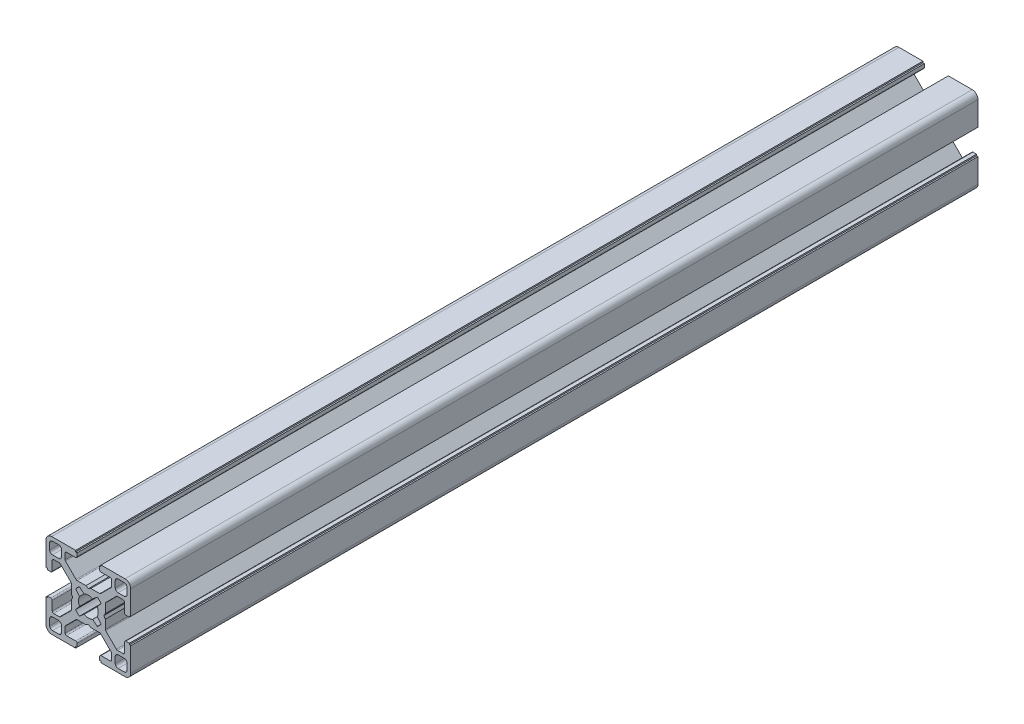
SolidWorks part; units mm, degrees
ref_plane "Front Plane" through (0, 0, 0) normal (0, 0, 1) x (1, 0, 0)
ref_plane "Top Plane" through (0, 0, 0) normal (0, 1, 0) x (1, 0, 0)
ref_plane "Right Plane" through (0, 0, 0) normal (1, 0, 0) x (0, 0, -1)
sketch "Sketch1" plane through (0, 0, 0) normal (0, 0, 1) x (1, 0, 0)
  line L0 (-15, 0) -> (15, 0) construction
  line L1 (0, -15) -> (0, 15) construction
  line L2 (-4.5, 15) -> (4.5, 15) construction
  line L3 (-4, -15) -> (4, -15) construction
  line L4 (-4.5, 15) -> (-4.5, 14.5)
  line L5 (-4.5, 14.5) -> (-4, 14.5)
  line L6 (-4, 14.5) -> (-4, 13.29)
  line L7 (-4.5, 12.79) -> (-7.7675, 12.79)
  line L8 (-8.2675, 12.29) -> (-8.2675, 10.2707)
  line L9 (-8.1211, 9.9171) -> (-4.3504, 6.1464)
  line L10 (-3.9968, 6) -> (0, 6)
  line L11 (0, 0) -> (-15, 15) construction
  line L12 (-4.5, 15) -> (-12.968, 15)
  line L14 (-12.705, 9.5135) -> (-10.5135, 9.5135)
  line L15 (-13.705, 10.5135) -> (-13.705, 12.705)
  line L16 (-12.705, 13.705) -> (-10.5135, 13.705)
  line L17 (-9.5135, 10.5135) -> (-9.5135, 12.705)
  line L18 (-13.705, 9.5135) -> (-9.5135, 13.705) construction
  line L19 (-13.705, 13.705) -> (-9.5135, 9.5135) construction
  line L20 (-3.1568, 4.5038) -> (-1.5303, 3.1477) construction
  line L21 (-4.5038, 3.1568) -> (-3.1477, 1.5303) construction
  line L22 (-6, 3.9968) -> (-6, 0)
  line L23 (-9.9171, 8.1211) -> (-6.1464, 4.3504)
  line L24 (-15, 4.5) -> (-15, 12.968)
  line L25 (-12.29, 8.2675) -> (-10.2707, 8.2675)
  line L26 (-12.79, 4.5) -> (-12.79, 7.7675)
  line L27 (-14.5, 4) -> (-13.29, 4)
  line L28 (-14.5, 4.5) -> (-14.5, 4)
  line L29 (-15, 4.5) -> (-14.5, 4.5)
  circle A0 centre (0, 0) radius 3.5
  arc A1 (-12.968, 15) -> (-15, 12.968) centre (-12.968, 12.968) ccw
  circle A2 centre (0, 0) radius 5.5 construction
  arc A3 (-10.5135, 9.5135) -> (-9.5135, 10.5135) centre (-10.5135, 10.5135) ccw
  arc A4 (-13.705, 12.705) -> (-12.705, 13.705) centre (-12.705, 12.705) cw
  arc A5 (-10.5135, 13.705) -> (-9.5135, 12.705) centre (-10.5135, 12.705) cw
  arc A6 (-12.705, 9.5135) -> (-13.705, 10.5135) centre (-12.705, 10.5135) cw
  arc A7 (-12.79, 4.5) -> (-13.29, 4) centre (-13.29, 4.5) cw
  arc A8 (-12.29, 8.2675) -> (-12.79, 7.7675) centre (-12.29, 7.7675) ccw
  arc A9 (-9.9171, 8.1211) -> (-10.2707, 8.2675) centre (-10.2707, 7.7675) ccw
  arc A10 (-6, 3.9968) -> (-6.1464, 4.3504) centre (-6.5, 3.9968) ccw
  arc A11 (-4.3504, 6.1464) -> (-3.9968, 6) centre (-3.9968, 6.5) ccw
  arc A12 (-4, 13.29) -> (-4.5, 12.79) centre (-4.5, 13.29) cw
  arc A13 (-7.7675, 12.79) -> (-8.2675, 12.29) centre (-7.7675, 12.29) ccw
  arc A14 (-8.2675, 10.2707) -> (-8.1211, 9.9171) centre (-7.7675, 10.2707) ccw
  point P4 (0, 0)
  point P8 (0, 0)
  point P13 (0, 15)
  point P15 (0, -15)
  point P16 (0, 6)
  point P23 (-11.6092, 11.6093)
  point P26 (0, 6)
  point P62 (-12.79, 4)
  point P65 (-12.79, 8.2675)
  point P68 (-10.0636, 8.2675)
  point P71 (-6, 4.2039)
  point P74 (-4.2039, 6)
  point P77 (-4, 12.79)
  point P80 (-8.2675, 12.79)
  point P83 (-8.2675, 10.0636)
  dimension "Center Hole Diameter" = 7
  dimension "D11" = 2.032
  dimension "D9" = 11
  dimension "D13" = 1
  dimension "D14" = 0.5
  dimension "Rail Height" = 30
  dimension "Rail Width" = 30
  dimension "T-Slot Width" = 8
  dimension "T-Slot Depth" = 9
  dimension "D1" = 9
  dimension "D2" = 45
  dimension "D3" = 8
  dimension "D4" = 2.21
  dimension "D5" = 16.535
  dimension "D7" = 2.54
  dimension "D6" = 1.295
  dimension "D8" = 1.246
  dimension "D10" = 10.36
  dimension "D12" = 1.905
sketch "Sketch2" plane through (0, 0, 0) normal (1, 0, 0) x (0, 0, -1)
  line L0 (-76.2, 0) -> (76.2, 0) construction
  line L2 (0, -15) -> (0, 15) construction
  line L3 (0, -15) -> (0, 15) construction
  line L4 (-76.2, -15) -> (-76.2, 15) construction
  line L5 (76.2, -15) -> (76.2, 15) construction
  point P0 (-38.7, 0)
  point P3 (0, 0)
  point P4 (38.7, 0)
  point P12 (-76.2, 0)
  point P14 (76.2, 0)
  dimension "Length" = 152.4
  dimension "D1" = 37.5
sketch "Sketch3" plane through (0, 0, 0) normal (0, 0, 1) x (1, 0, 0)
  line L0 (-4.5038, 3.1568) -> (-3.1477, 1.5303)
  line L1 (0, 3.5) -> (0, 5.5)
  line L2 (-5.5, 0) -> (-3.5, 0)
  line L7 (-6, 3.9968) -> (-6, 0) construction
  line L31 (-9.9171, 8.1211) -> (-6.1464, 4.3504) construction
  line L117 (-12.29, 8.2675) -> (-10.2707, 8.2675) construction
  line L118 (-12.79, 4.5) -> (-12.79, 7.7675) construction
  line L157 (-12.705, 9.5135) -> (-10.5135, 9.5135)
  line L158 (-9.5135, 10.5135) -> (-9.5135, 12.705)
  line L163 (-10.5135, 13.705) -> (-12.705, 13.705)
  line L164 (-13.705, 12.705) -> (-13.705, 10.5135)
  line L165 (-12.705, 9.5135) -> (-10.5135, 9.5135)
  line L166 (-9.5135, 10.5135) -> (-9.5135, 12.705)
  line L167 (-10.5135, 13.705) -> (-12.705, 13.705)
  line L168 (-13.705, 12.705) -> (-13.705, 10.5135)
  line L169 (-14.5, 4) -> (-13.29, 4) construction
  line L170 (-14.5, 4.5) -> (-14.5, 4) construction
  line L171 (-15, 4.5) -> (-14.5, 4.5) construction
  line L172 (-15, 4.5) -> (-15, 12.968) construction
  line L173 (-4.5, 15) -> (-12.968, 15) construction
  line L174 (-4.5, 15) -> (-4.5, 14.5) construction
  line L175 (-4.5, 14.5) -> (-4, 14.5) construction
  line L176 (-4, 14.5) -> (-4, 13.29) construction
  line L177 (-4.5, 12.79) -> (-7.7675, 12.79) construction
  line L178 (-8.2675, 12.29) -> (-8.2675, 10.2707) construction
  line L179 (-8.1211, 9.9171) -> (-4.3504, 6.1464) construction
  line L180 (-3.9968, 6) -> (0, 6) construction
  line L181 (-6, 3.9968) -> (-6, 0.866)
  line L182 (-9.9171, 8.1211) -> (-6.1464, 4.3504)
  line L183 (-12.29, 8.2675) -> (-10.2707, 8.2675)
  line L184 (-12.79, 4.5) -> (-12.79, 7.7675)
  line L185 (-14.5, 4) -> (-13.29, 4)
  line L186 (-14.5, 4.5) -> (-14.5, 4)
  line L187 (-15, 4.5) -> (-14.5, 4.5)
  line L188 (-15, 4.5) -> (-15, 12.968)
  line L189 (-4.5, 15) -> (-12.968, 15)
  line L190 (-4.5, 15) -> (-4.5, 14.5)
  line L191 (-4.5, 14.5) -> (-4, 14.5)
  line L192 (-4, 14.5) -> (-4, 13.29)
  line L193 (-4.5, 12.79) -> (-7.7675, 12.79)
  line L194 (-8.2675, 12.29) -> (-8.2675, 10.2707)
  line L195 (-8.1211, 9.9171) -> (-4.3504, 6.1464)
  line L196 (-3.9968, 6) -> (-0.866, 6)
  line L197 (-0.866, 6) -> (0, 5.5)
  line L198 (0, -15) -> (0, 15) construction
  line L199 (0, 0) -> (-15, 15) construction
  line L200 (0, 0) -> (-15, 15) construction
  line L201 (-3.1568, 4.5038) -> (-1.5303, 3.1477) construction
  line L202 (-3.1568, 4.5038) -> (-1.5303, 3.1477)
  line L203 (-6, 0.866) -> (-5.5, 0)
  line L204 (-15, 0) -> (15, 0) construction
  line L205 (-15, 0) -> (15, 0) construction
  line L206 (0, -15) -> (0, 15) construction
  arc A0 (-3.5, 0) -> (-3.1477, 1.5303) centre (0, 0) cw
  arc A10 (-6, 3.9968) -> (-6.1464, 4.3504) centre (-6.5, 3.9968) ccw construction
  circle A16 centre (0, 0) radius 3.5
  arc A18 (0, 3.5) -> (-1.5303, 3.1477) centre (0, 0) ccw
  arc A20 (-9.9171, 8.1211) -> (-10.2707, 8.2675) centre (-10.2707, 7.7675) ccw construction
  arc A22 (-12.29, 8.2675) -> (-12.79, 7.7675) centre (-12.29, 7.7675) ccw construction
  arc A28 (-13.29, 4) -> (-12.79, 4.5) centre (-13.29, 4.5) ccw construction
  arc A29 (-10.5135, 9.5135) -> (-9.5135, 10.5135) centre (-10.5135, 10.5135) ccw
  arc A30 (-9.5135, 12.705) -> (-10.5135, 13.705) centre (-10.5135, 12.705) ccw
  arc A31 (-12.705, 13.705) -> (-13.705, 12.705) centre (-12.705, 12.705) ccw
  arc A32 (-13.705, 10.5135) -> (-12.705, 9.5135) centre (-12.705, 10.5135) ccw
  arc A33 (-10.5135, 9.5135) -> (-9.5135, 10.5135) centre (-10.5135, 10.5135) ccw
  arc A34 (-9.5135, 12.705) -> (-10.5135, 13.705) centre (-10.5135, 12.705) ccw
  arc A35 (-12.705, 13.705) -> (-13.705, 12.705) centre (-12.705, 12.705) ccw
  arc A36 (-13.705, 10.5135) -> (-12.705, 9.5135) centre (-12.705, 10.5135) ccw
  arc A37 (-12.968, 15) -> (-15, 12.968) centre (-12.968, 12.968) ccw construction
  arc A38 (-4.5, 12.79) -> (-4, 13.29) centre (-4.5, 13.29) ccw construction
  arc A39 (-7.7675, 12.79) -> (-8.2675, 12.29) centre (-7.7675, 12.29) ccw construction
  arc A40 (-8.2675, 10.2707) -> (-8.1211, 9.9171) centre (-7.7675, 10.2707) ccw construction
  arc A41 (-4.3504, 6.1464) -> (-3.9968, 6) centre (-3.9968, 6.5) ccw construction
  arc A42 (-6, 3.9968) -> (-6.1464, 4.3504) centre (-6.5, 3.9968) ccw
  arc A43 (-9.9171, 8.1211) -> (-10.2707, 8.2675) centre (-10.2707, 7.7675) ccw
  arc A44 (-12.29, 8.2675) -> (-12.79, 7.7675) centre (-12.29, 7.7675) ccw
  arc A45 (-13.29, 4) -> (-12.79, 4.5) centre (-13.29, 4.5) ccw
  arc A46 (-12.968, 15) -> (-15, 12.968) centre (-12.968, 12.968) ccw
  arc A47 (-4.5, 12.79) -> (-4, 13.29) centre (-4.5, 13.29) ccw
  arc A48 (-7.7675, 12.79) -> (-8.2675, 12.29) centre (-7.7675, 12.29) ccw
  arc A49 (-8.2675, 10.2707) -> (-8.1211, 9.9171) centre (-7.7675, 10.2707) ccw
  arc A50 (-4.3504, 6.1464) -> (-3.9968, 6) centre (-3.9968, 6.5) ccw
  circle A51 centre (0, 0) radius 5.5 construction
  arc A52 (-3.1568, 4.5038) -> (-4.5038, 3.1568) centre (0, 0) ccw
  dimension "D3" = 60
  dimension "D4" = 60
  dimension "D1" = 0
  dimension "D2" = 0
extrude "Boss-Extrude1" add sketch "Sketch3" along normal mid plane 300
pattern_circular "CirPattern1" count 4 over 360 about axis through (0, 0, 76.2) along (0, 0, -1) of "Boss-Extrude1"
ref_plane "Contact Plane1" through (15, 0, 0) normal (1, 0, 0) x (0, 0, -1)
ref_plane "Contact Plane2" through (0, -15, 0) normal (0, 1, 0) x (1, 0, 0)
ref_plane "Contact Plane3" through (-15, 0, 0) normal (1, 0, 0) x (0, 0, -1)
ref_plane "Contact Plane4" through (0, 15, 0) normal (0, 1, 0) x (1, 0, 0)
equation "\"D1@Sketch2\" = \"Rail Height@Sketch1\" * 1.25"
equation "\"D1@Sketch1\"=\"T-Slot Width@Sketch1\"+1mm"
equation "\"D3@Sketch1\"=\"T-Slot Width@Sketch1\""
equation "\"D1@Boss-Extrude1\"=\"Width\""
equation "\"Width\" = 300mm"
